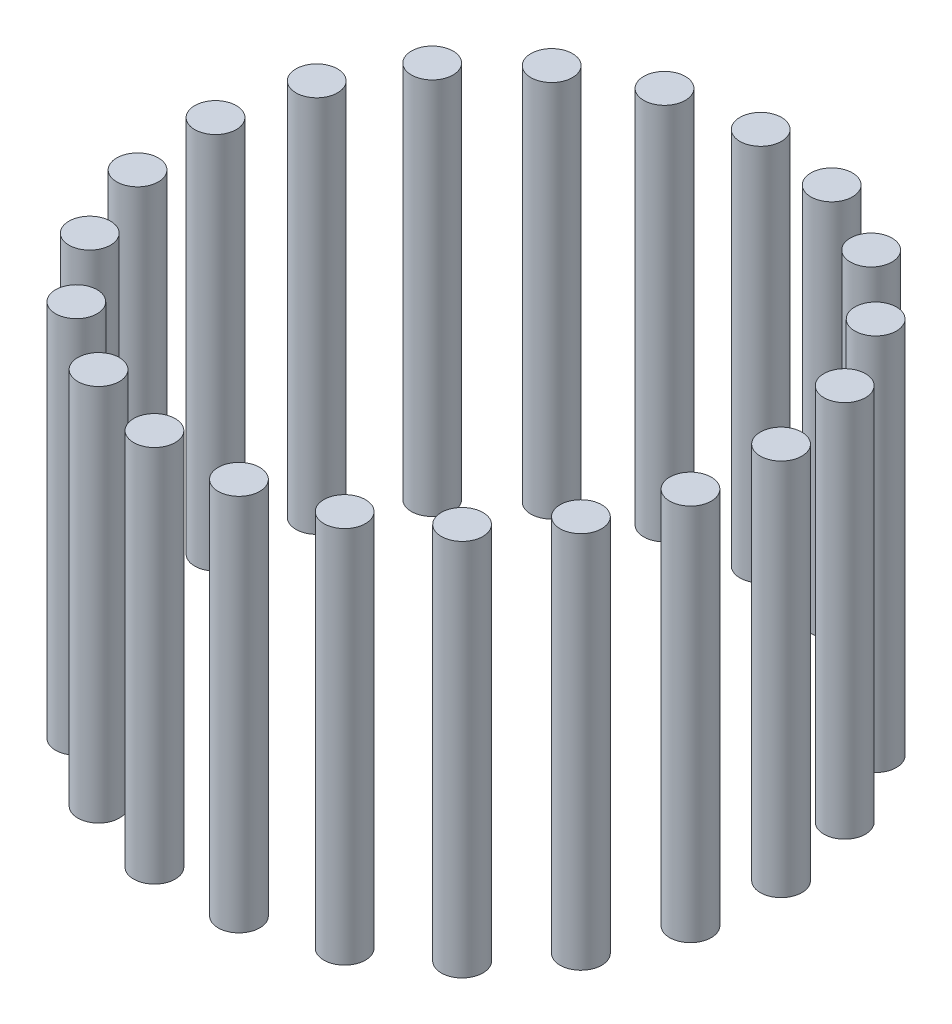
SolidWorks part; units mm, degrees
ref_plane "Front Plane" through (0, 0, 0) normal (0, 0, 1) x (1, 0, 0)
ref_plane "Top Plane" through (0, 0, 0) normal (0, 1, 0) x (1, 0, 0)
ref_plane "Right Plane" through (0, 0, 0) normal (1, 0, 0) x (0, 0, -1)
sketch "Sketch1" plane through (0, 0, 0) normal (0, 1, 0) x (1, 0, 0)
  circle A1 centre (0, 75) radius 5.5
  circle A2 centre (22.1066, 71.668) radius 5.5
  circle A3 centre (42.249, 61.9679) radius 5.5
  circle A4 centre (58.6374, 46.7617) radius 5.5
  circle A5 centre (69.8155, 27.4006) radius 5.5
  circle A6 centre (74.7903, 5.6048) radius 5.5
  circle A7 centre (73.1196, -16.6891) radius 5.5
  circle A8 centre (64.9519, -37.5) radius 5.5
  circle A9 centre (51.013, -54.9789) radius 5.5
  circle A10 centre (32.5413, -67.5727) radius 5.5
  circle A11 centre (11.1782, -74.1623) radius 5.5
  circle A12 centre (-11.1782, -74.1623) radius 5.5
  circle A13 centre (-32.5413, -67.5727) radius 5.5
  circle A14 centre (-51.013, -54.9789) radius 5.5
  circle A15 centre (-64.9519, -37.5) radius 5.5
  circle A16 centre (-73.1196, -16.6891) radius 5.5
  circle A17 centre (-74.7903, 5.6048) radius 5.5
  circle A18 centre (-69.8155, 27.4006) radius 5.5
  circle A19 centre (-58.6374, 46.7617) radius 5.5
  circle A20 centre (-42.249, 61.9679) radius 5.5
  circle A21 centre (-22.1066, 71.668) radius 5.5
  point P48 (0, 0)
  dimension "D1" = 21
extrude "Boss-Extrude1" add sketch "Sketch1" along normal blind 100
